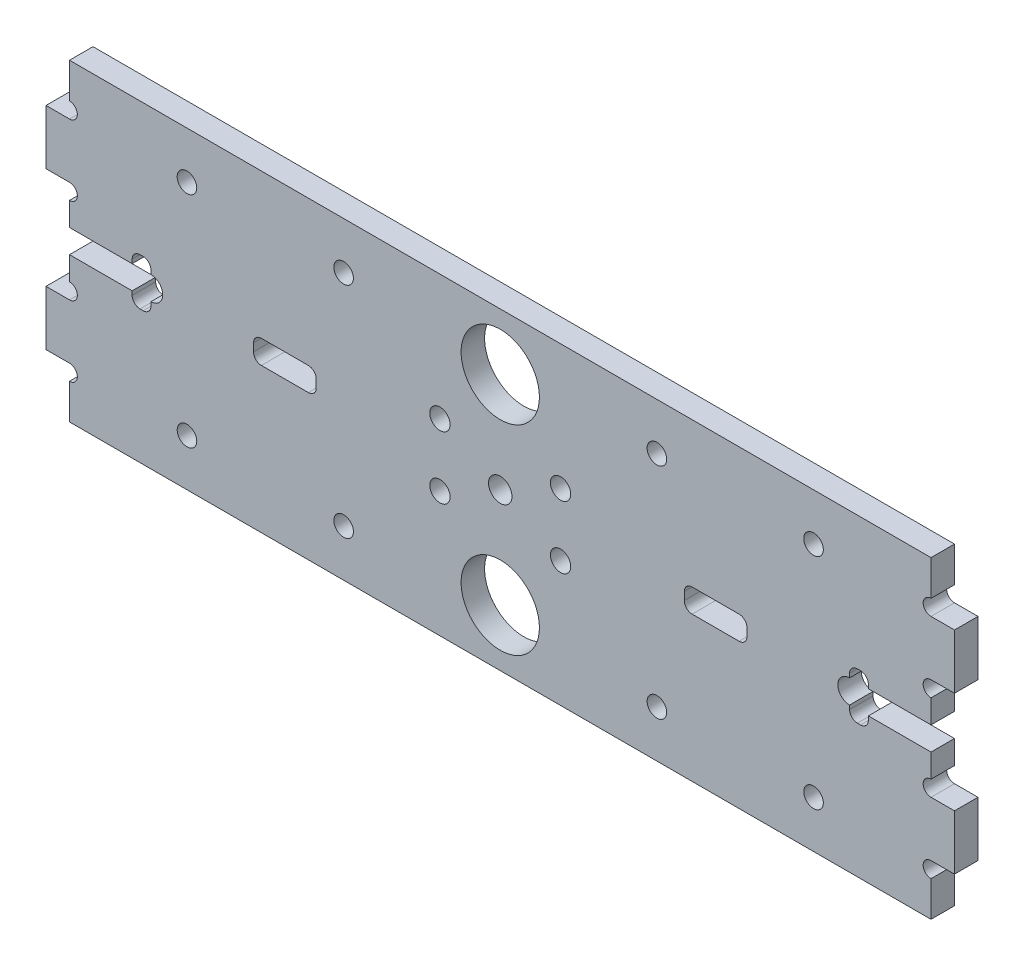
SolidWorks part; units mm, degrees
material "Acrylic (Medium-high impact)"
ref_plane "Front Plane" through (0, 0, 0) normal (0, 0, 1) x (1, 0, 0)
ref_plane "Top Plane" through (0, 0, 0) normal (0, 1, 0) x (1, 0, 0)
ref_plane "Right Plane" through (0, 0, 0) normal (1, 0, 0) x (0, 0, -1)
sketch "Sketch1" plane through (0, 0, 0) normal (0, 0, 1) x (1, 0, 0)
  line L0 (0, 20) -> (0, -20) construction
  line L1 (-55, 20) -> (55, 20)
  line L2 (-55, 20) -> (-55, -20)
  line L3 (-55, -20) -> (55, -20)
  line L4 (55, 20) -> (55, -20)
  line L5 (55, 0) -> (-55, 0) construction
  point P8 (0, 0)
extrude "Boss-Extrude1" add sketch "Sketch1" along normal blind 3
sketch "Sketch2" plane through (0, 0, 3) normal (0, 0, 1) x (1, 0, 0)
  line L0 (-55, 0) -> (55, 0) construction
  line L1 (-55, 20) -> (-55, -20) construction
  line L2 (55, -20) -> (55, 20) construction
  line L3 (55, 0) -> (55, -20) construction
  line L4 (55, 0) -> (55, 20) construction
  line L5 (55, 20) -> (58, 20) construction
  line L6 (58, 20) -> (58, -20) construction
  line L7 (58, -20) -> (55, -20) construction
  line L8 (0, 20) -> (0, -20) construction
  line L9 (55, 20) -> (-55, 20) construction
  line L10 (-55, -20) -> (55, -20) construction
  line L11 (55, -10) -> (58, -10) construction
  line L12 (55, 10) -> (58, 10) construction
  line L13 (58, 10) -> (58, 13.5)
  line L14 (58, 10) -> (58, 6.5)
  line L15 (58, 6.5) -> (55, 6.5)
  line L16 (55, 6.5) -> (55, 13.5)
  line L17 (55, 13.5) -> (58, 13.5)
  line L18 (55, -10) -> (55, -6.5)
  line L19 (55, -6.5) -> (58, -6.5)
  line L20 (58, -6.5) -> (58, -13.5)
  line L21 (58, -13.5) -> (55, -13.5)
  line L22 (55, -13.5) -> (55, -10)
  line L23 (-55, 6.5) -> (-55, 13.5)
  line L24 (-55, -13.5) -> (-55, -10)
  line L25 (-55, -10) -> (-55, -6.5)
  line L26 (-55, 10) -> (-58, 10) construction
  line L27 (-55, -10) -> (-58, -10) construction
  line L28 (-58, -20) -> (-55, -20) construction
  line L29 (-58, 20) -> (-58, -20) construction
  line L30 (-55, 20) -> (-58, 20) construction
  line L31 (-58, -13.5) -> (-55, -13.5)
  line L32 (-58, -6.5) -> (-58, -13.5)
  line L33 (-55, -6.5) -> (-58, -6.5)
  line L34 (-55, 13.5) -> (-58, 13.5)
  line L35 (-58, 6.5) -> (-55, 6.5)
  line L36 (-58, 10) -> (-58, 6.5)
  line L37 (-58, 10) -> (-58, 13.5)
extrude "Boss-Extrude2" add sketch "Sketch2" against normal blind 3
sketch "Sketch3" plane through (0, 0, 3) normal (0, 0, 1) x (1, 0, 0)
  line L0 (-55, 0) -> (55, 0) construction
  line L1 (-55, 6.5) -> (-55, -6.5) construction
  line L2 (55, -6.5) -> (55, 6.5) construction
  line L3 (-55, 13.5) -> (-55, 14.5) construction
  line L4 (-55, 20) -> (-55, 13.5) construction
  line L5 (-55, 14.5) -> (55, 14.5) construction
  line L6 (55, 13.5) -> (55, 20) construction
  line L7 (55, 14.5) -> (55, 5.5) construction
  line L8 (55, 5.5) -> (-55, 5.5) construction
  line L9 (-55, -6.5) -> (-55, -5.5) construction
  line L10 (-55, -5.5) -> (55, -5.5) construction
  line L11 (55, -5.5) -> (55, -14.5) construction
  line L12 (55, -20) -> (55, -13.5) construction
  line L13 (55, -14.5) -> (-55, -14.5) construction
  line L14 (-55, -13.5) -> (-55, -20) construction
  circle A0 centre (0, 0) radius 1.5
  circle A1 centre (-55, 14.5) radius 1
  circle A2 centre (-55, 5.5) radius 1
  circle A3 centre (-55, -5.5) radius 1
  circle A4 centre (-55, -14.5) radius 1
  circle A5 centre (55, 14.5) radius 1
  circle A6 centre (55, 5.5) radius 1
  circle A7 centre (55, -5.5) radius 1
  circle A8 centre (55, -14.5) radius 1
  line M2 (-55, 20) -> (-55, 13.5)
  line M6 (-55, 6.5) -> (-55, -6.5)
  line M10 (-55, -13.5) -> (-55, -20)
  line M12 (55, -20) -> (55, -13.5)
  line M16 (55, -6.5) -> (55, 6.5)
  line M20 (55, 13.5) -> (55, 20)
extrude "Cut-Extrude1" cut sketch "Sketch3" against normal blind 3 contours A4 M10 | A3 M6 | A2 M6 | A1 M2 | A0 | A7 M16 | A8 M12 | A6 M16 | A5 M20 region at (0, 0, 3) region at (-54.5756, 14.5, 3) region at (-54.5756, 5.5, 3) region at (-54.5756, -5.5, 3) region at (-54.5756, -14.5, 3) region at (54.5756, 14.5, 3) region at (54.5756, -5.5, 3) region at (54.5756, 5.5, 3) region at (54.5756, -14.5, 3)
sketch "Sketch4" plane through (0, 0, 3) normal (0, 0, 1) x (1, 0, 0)
  line L0 (-55, 0) -> (55, 0) construction
  line L1 (-55, 4.5) -> (-55, -4.5) construction
  line L2 (55, -4.5) -> (55, 4.5) construction
  line L3 (55, 0) -> (55, -1.5) construction
  line L4 (55, -1.5) -> (-55, -1.5) construction
  line L5 (-55, -1.5) -> (-55, 1.5) construction
  line L6 (-55, 1.5) -> (55, 1.5) construction
  line L7 (55, 1.5) -> (47, 1.5) construction
  line L8 (47, 20) -> (47, -20) construction
  line L9 (55, 20) -> (-55, 20) construction
  line L10 (-55, -20) -> (55, -20) construction
  line L11 (-55, 1.5) -> (-47, 1.5) construction
  line L12 (-47, 20) -> (-47, -20) construction
  line L13 (-47, 20) -> (-44.6, 20) construction
  line L14 (-44.6, 20) -> (-44.6, -20) construction
  line L15 (47, 20) -> (44.6, 20) construction
  line L16 (44.6, 20) -> (44.6, -20) construction
  line L17 (55, 1.5) -> (55, 3) construction
  line L18 (55, 3) -> (-55, 3) construction
  line L19 (-55, 3) -> (-55, -3) construction
  line L20 (-55, -3) -> (55, -3) construction
  line L21 (-44.6, 0) -> (-43.1, 0) construction
  line L22 (44.6, 0) -> (43.1, 0) construction
  line L24 (-55, 1.5) -> (-47, 1.5)
  line L25 (-55, 1.5) -> (-55, -1.5)
  line L26 (-55, -1.5) -> (-47, -1.5)
  line L27 (-47, 1.5) -> (-47, -1.5)
  line L28 (-47, 3) -> (-44.6, 3)
  line L29 (-47, 3) -> (-47, -3)
  line L30 (-47, -3) -> (-44.6, -3)
  line L31 (-44.6, 3) -> (-44.6, -3)
  line L32 (44.6, 3) -> (47, 3)
  line L33 (44.6, 3) -> (44.6, -3)
  line L34 (44.6, -3) -> (47, -3)
  line L35 (47, 3) -> (47, -3)
  line L36 (47, 1.5) -> (55, 1.5)
  line L37 (47, 1.5) -> (47, -1.5)
  line L38 (47, -1.5) -> (55, -1.5)
  line L39 (55, 1.5) -> (55, -1.5)
  arc A0 (44.6, 1.5) -> (44.6, -1.5) centre (44.6, 0) ccw
  arc A1 (-44.6, 1.5) -> (-44.6, -1.5) centre (-44.6, 0) cw
  line M10 (-55, 4.5) -> (-55, -4.5)
  line M24 (55, -4.5) -> (55, 4.5)
extrude "Cut-Extrude2" cut sketch "Sketch4" against normal blind 3 contours L27 L24 L26 M10 | L31 L28 L29 L27 L30 | A1 L31 | L35 L32 L33 L34 | L33 A0 | L35 L38 L36 M24 region at (-51, 0, 3) region at (-45.8, 0, 3) region at (-43.9634, 0, 3) region at (45.8, 0, 3) region at (43.9634, 0, 3) region at (51, 0, 3)
fillet "Fillet6" radius 1 8 edges at (-44.6, 3, 1.5) (-47, 3, 1.5) (-44.6, -3, 1.5) (-47, -3, 1.5) (47, 3, 1.5) (44.6, 3, 1.5) (47, -3, 1.5) (44.6, -3, 1.5)
sketch "Sketch5" plane through (0, 0, 3) normal (0, 0, 1) x (1, 0, 0)
  line L0 (-55, -1.5) -> (-55, 1.5) construction
  line L1 (55, -1.5) -> (55, 1.5) construction
  line L2 (-55, 0) -> (0, 0) construction
  line L3 (0, 0) -> (55, 0) construction
  line L4 (-27.5, 0) -> (-27.5, 1.5) construction
  line L5 (-27.5, 1.5) -> (-23.5, 1.5) construction
  line L6 (-23.5, 1.5) -> (-23.5, -1.5) construction
  line L7 (-23.5, -1.5) -> (-31.5, -1.5) construction
  line L8 (-31.5, -1.5) -> (-31.5, 1.5) construction
  line L9 (-31.5, 1.5) -> (-27.5, 1.5) construction
  line L10 (27.5, 0) -> (27.5, 1.5) construction
  line L11 (27.5, 1.5) -> (31.5, 1.5) construction
  line L12 (31.5, 1.5) -> (31.5, -1.5) construction
  line L13 (31.5, -1.5) -> (23.5, -1.5) construction
  line L14 (23.5, -1.5) -> (23.5, 1.5) construction
  line L15 (23.5, 1.5) -> (27.5, 1.5) construction
  line L17 (-31.5, 1.5) -> (-23.5, 1.5)
  line L18 (-31.5, 1.5) -> (-31.5, -1.5)
  line L19 (-31.5, -1.5) -> (-23.5, -1.5)
  line L20 (-23.5, 1.5) -> (-23.5, -1.5)
  line L21 (23.5, 1.5) -> (31.5, 1.5)
  line L22 (23.5, 1.5) -> (23.5, -1.5)
  line L23 (23.5, -1.5) -> (31.5, -1.5)
  line L24 (31.5, 1.5) -> (31.5, -1.5)
extrude "Cut-Extrude3" cut sketch "Sketch5" against normal blind 10
fillet "Fillet7" radius 1 8 edges at (-31.5, -1.5, 1.5) (-31.5, 1.5, 1.5) (-23.5, 1.5, 1.5) (23.5, -1.5, 1.5) (23.5, 1.5, 1.5) (31.5, 1.5, 1.5) (31.5, -1.5, 1.5) (-23.5, -1.5, 1.5)
sketch "Sketch6" plane through (0, 0, 3) normal (0, 0, 1) x (1, 0, 0)
  line L0 (0, 0) -> (0, 20) construction
  line L1 (55, 20) -> (-55, 20) construction
  line L2 (0, 20) -> (0, 14) construction
  line L3 (0, 0) -> (0, -20) construction
  line L4 (-55, -20) -> (55, -20) construction
  line L5 (0, -20) -> (0, -14) construction
  circle A0 centre (0, 14) radius 1.25
  circle A1 centre (0, -14) radius 1.25
  circle A2 centre (20, -14) radius 1.25
  circle A3 centre (20, 14) radius 1.25
  circle A4 centre (40, -14) radius 1.25
  circle A5 centre (40, 14) radius 1.25
  circle A6 centre (-20, -14) radius 1.25
  circle A7 centre (-20, 14) radius 1.25
  circle A8 centre (-40, -14) radius 1.25
  circle A9 centre (-40, 14) radius 1.25
  dimension "D1" = 3
  dimension "D2" = 3
extrude "Cut-Extrude4" cut sketch "Sketch6" against normal through all contours A8 | A6 | A1 | A2 | A4 | A5 | A3 | A0 | A7 | A9 region at (0, 14, 3) region at (0, -14, 3) region at (20, -14, 3) region at (20, 14, 3) region at (40, -14, 3) region at (40, 14, 3) region at (-20, -14, 3) region at (-20, 14, 3) region at (-40, -14, 3) region at (-40, 14, 3)
sketch "Sketch7" plane through (0, 0, 3) normal (0, 0, 1) x (1, 0, 0)
  line L0 (0, 0) -> (0, 4) construction
  line L1 (0, 4) -> (7.7, 4) construction
  line L2 (7.7, 4) -> (7.7, -4) construction
  line L3 (7.7, -4) -> (-7.7, -4) construction
  line L4 (-7.7, -4) -> (-7.7, 4) construction
  line L5 (-7.7, 4) -> (0, 4) construction
  circle A0 centre (-7.7, 4) radius 1.3
  circle A1 centre (7.7, 4) radius 1.3
  circle A2 centre (7.7, -4) radius 1.3
  circle A3 centre (-7.7, -4) radius 1.3
extrude "Cut-Extrude5" cut sketch "Sketch7" against normal blind 10
sketch "Sketch8" plane through (0, 0, 3) normal (0, 0, 1) x (1, 0, 0)
  circle A0 centre (0, -12.75) radius 5
  circle A1 centre (0, -14) radius 1.25 construction
  circle A2 centre (0, 12.75) radius 5
  circle A3 centre (0, 14) radius 1.25 construction
extrude "Cut-Extrude6" cut sketch "Sketch8" against normal blind 10
